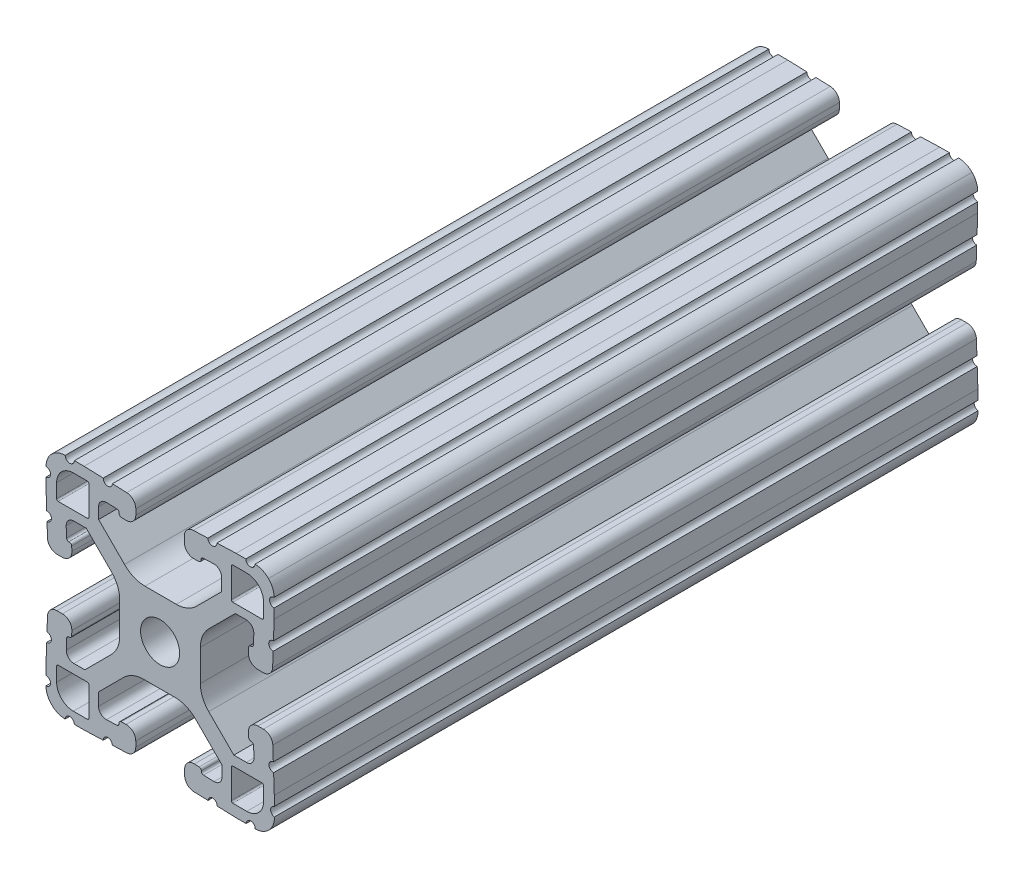
SolidWorks part; units mm, degrees
material "6061-T6 (SS)"
ref_plane "Front Plane" through (0, 0, 0) normal (0, 0, 1) x (1, 0, 0)
ref_plane "Top Plane" through (0, 0, 0) normal (0, 1, 0) x (1, 0, 0)
ref_plane "Right Plane" through (0, 0, 0) normal (1, 0, 0) x (0, 0, -1)
ref_plane "Plane1" through (0, 0, -25.4) normal (0, 0, -1) x (-1, 0, 0)
sketch "Sketch1" plane through (0, 0, -25.4) normal (0, 0, -1) x (-1, 0, 0)
  line L0 (-83.3577, 88.2941) -> (-83.3577, 93.1709)
  line L1 (-83.1037, 93.4249) -> (-80.767, 93.4249)
  line L2 (-77.9729, 90.6309) -> (-77.9729, 88.2941)
  line L3 (-78.2269, 88.0401) -> (-83.1037, 88.0401)
  line L4 (-83.3577, 59.2291) -> (-83.3577, 64.1059)
  line L5 (-83.1037, 64.3599) -> (-78.2269, 64.3599)
  line L6 (-77.9729, 64.1059) -> (-77.9729, 61.7691)
  line L7 (-80.767, 58.9751) -> (-83.1037, 58.9751)
  line L8 (-107.1423, 93.1709) -> (-107.1423, 88.2941)
  line L9 (-107.3963, 88.0401) -> (-112.2731, 88.0401)
  line L10 (-112.5271, 88.2941) -> (-112.5271, 90.6309)
  line L11 (-109.733, 93.4249) -> (-107.3963, 93.4249)
  line L12 (-107.1423, 64.1059) -> (-107.1423, 59.2291)
  line L13 (-107.3963, 58.9751) -> (-109.733, 58.9751)
  line L14 (-112.5271, 61.7691) -> (-112.5271, 64.1059)
  line L15 (-112.2731, 64.3599) -> (-107.3963, 64.3599)
  line L16 (-88.0437, 91.8626) -> (-86.2967, 91.9236)
  line L17 (-84.9824, 90.6544) -> (-84.9824, 88.8002)
  line L18 (-84.9824, 88.8002) -> (-89.3066, 84.476)
  line L19 (-92.7196, 83.0295) -> (-97.9616, 83.0295)
  line L20 (-101.3202, 84.4207) -> (-105.516, 88.6165)
  line L21 (-105.516, 88.6165) -> (-105.516, 90.7313)
  line L22 (-104.2017, 92.0006) -> (-102.4547, 91.9396)
  line L23 (-101.7262, 91.1059) -> (-100.9297, 91.0781)
  line L24 (-99.2999, 92.6519) -> (-99.2999, 93.5668)
  line L25 (-100.8197, 95.1407) -> (-103.2119, 95.2242)
  line L26 (-104.735, 95.2774) -> (-107.9359, 95.3892)
  line L27 (-107.9359, 95.3892) -> (-109.5615, 95.3892)
  line L28 (-114.2859, 90.6648) -> (-114.2859, 89.0392)
  line L29 (-114.2859, 89.0392) -> (-114.1741, 85.8383)
  line L30 (-114.1209, 84.3152) -> (-114.0374, 81.9231)
  line L31 (-112.4635, 80.4032) -> (-111.5486, 80.4032)
  line L32 (-109.9748, 82.033) -> (-110.0026, 82.8295)
  line L33 (-110.8377, 83.5577) -> (-110.8987, 85.3047)
  line L34 (-109.6294, 86.619) -> (-107.8072, 86.619)
  line L35 (-107.8072, 86.619) -> (-103.3649, 82.1768)
  line L36 (-101.9737, 78.8182) -> (-101.9737, 73.576)
  line L37 (-103.3649, 70.2174) -> (-107.5607, 66.0217)
  line L38 (-107.5607, 66.0217) -> (-109.6524, 66.0217)
  line L39 (-110.9217, 67.336) -> (-110.8607, 69.083)
  line L40 (-110.0322, 69.8124) -> (-110.0043, 70.6089)
  line L41 (-111.5782, 72.2387) -> (-112.4931, 72.2387)
  line L42 (-114.0669, 70.7189) -> (-114.1505, 68.3267)
  line L43 (-114.2036, 66.8036) -> (-114.3154, 63.6027)
  line L44 (-114.3154, 63.6027) -> (-114.3154, 61.9626)
  line L45 (-109.6111, 57.1437) -> (-107.9855, 57.1437)
  line L46 (-107.9855, 57.1437) -> (-104.7846, 57.2555)
  line L47 (-103.2615, 57.3086) -> (-100.8694, 57.3922)
  line L48 (-99.3495, 58.966) -> (-99.3495, 59.8809)
  line L49 (-100.9794, 61.4548) -> (-101.7758, 61.4269)
  line L50 (-102.5054, 60.599) -> (-104.2524, 60.538)
  line L51 (-105.5667, 61.8072) -> (-105.5667, 63.6295)
  line L52 (-105.5667, 63.6295) -> (-101.1311, 68.065)
  line L53 (-97.7725, 69.4562) -> (-92.5304, 69.4562)
  line L54 (-89.1717, 68.065) -> (-84.976, 63.8692)
  line L55 (-84.976, 63.8692) -> (-84.976, 61.7811)
  line L56 (-86.2903, 60.5118) -> (-88.0373, 60.5728)
  line L57 (-88.7596, 61.4332) -> (-89.5561, 61.461)
  line L58 (-91.1859, 59.8872) -> (-91.1859, 58.9723)
  line L59 (-89.6661, 57.3985) -> (-87.2739, 57.3149)
  line L60 (-85.7508, 57.2617) -> (-82.5499, 57.15)
  line L61 (-82.5499, 57.15) -> (-80.9244, 57.15)
  line L62 (-76.2, 61.8744) -> (-76.2, 63.4999)
  line L63 (-76.2, 63.4999) -> (-76.3117, 66.7008)
  line L64 (-76.3649, 68.2239) -> (-76.4484, 70.6161)
  line L65 (-78.0223, 72.1359) -> (-78.9372, 72.1359)
  line L66 (-80.511, 70.5061) -> (-80.4832, 69.7096)
  line L67 (-79.6552, 68.9801) -> (-79.5942, 67.2331)
  line L68 (-80.8634, 65.9188) -> (-82.6857, 65.9188)
  line L69 (-82.6857, 65.9188) -> (-87.1213, 70.3543)
  line L70 (-88.5125, 73.7128) -> (-88.5126, 78.955)
  line L71 (-87.1214, 82.3137) -> (-82.9257, 86.5095)
  line L72 (-82.9257, 86.5095) -> (-80.8375, 86.5095)
  line L73 (-79.5682, 85.1951) -> (-79.6293, 83.4482)
  line L74 (-80.4896, 82.7258) -> (-80.5175, 81.9294)
  line L75 (-78.9436, 80.2995) -> (-78.0287, 80.2995)
  line L76 (-76.4549, 81.8194) -> (-76.3713, 84.2115)
  line L77 (-76.3182, 85.7346) -> (-76.2064, 88.9355)
  line L78 (-76.2064, 88.9355) -> (-76.2064, 90.5611)
  line L79 (-80.9308, 95.2855) -> (-82.5564, 95.2855)
  line L80 (-82.5564, 95.2855) -> (-85.7573, 95.1737)
  line L81 (-87.2803, 95.1205) -> (-89.6725, 95.037)
  line L82 (-91.1924, 93.4632) -> (-91.1924, 92.5483)
  line L83 (-89.5625, 90.9744) -> (-88.7661, 91.0023)
  arc A0 (-83.3577, 93.1709) -> (-83.1037, 93.4249) centre (-83.1037, 93.1709) cw
  arc A1 (-80.767, 93.4249) -> (-77.9729, 90.6309) centre (-80.7669, 90.6309) cw
  arc A2 (-77.9729, 88.2941) -> (-78.2269, 88.0401) centre (-78.2269, 88.2941) cw
  arc A3 (-83.1037, 88.0401) -> (-83.3577, 88.2941) centre (-83.1037, 88.2941) cw
  arc A4 (-83.1037, 58.9751) -> (-83.3577, 59.2291) centre (-83.1037, 59.2291) cw
  arc A5 (-83.3577, 64.1059) -> (-83.1037, 64.3599) centre (-83.1037, 64.1059) cw
  arc A6 (-78.2269, 64.3599) -> (-77.9729, 64.1059) centre (-78.2269, 64.1059) cw
  arc A7 (-77.9729, 61.7691) -> (-80.767, 58.9751) centre (-80.7669, 61.7691) cw
  arc A8 (-107.3963, 93.4249) -> (-107.1423, 93.1709) centre (-107.3963, 93.1709) cw
  arc A9 (-107.1423, 88.2941) -> (-107.3963, 88.0401) centre (-107.3963, 88.2941) cw
  arc A10 (-112.2731, 88.0401) -> (-112.5271, 88.2941) centre (-112.2731, 88.2941) cw
  arc A11 (-112.5271, 90.6309) -> (-109.733, 93.4249) centre (-109.7331, 90.6309) cw
  arc A12 (-107.1423, 59.2291) -> (-107.3963, 58.9751) centre (-107.3963, 59.2291) cw
  arc A13 (-109.733, 58.9751) -> (-112.5271, 61.7691) centre (-109.7331, 61.7691) cw
  arc A14 (-112.5271, 64.1059) -> (-112.2731, 64.3599) centre (-112.2731, 64.1059) cw
  arc A15 (-107.3963, 64.3599) -> (-107.1423, 64.1059) centre (-107.3963, 64.1059) cw
  circle A16 centre (-95.25, 76.2) radius 3.2639
  arc A17 (-88.7661, 91.0023) -> (-88.3984, 91.383) centre (-88.7794, 91.383) ccw
  arc A18 (-88.3984, 91.383) -> (-88.0437, 91.8626) centre (-88.0304, 91.4819) cw
  arc A19 (-86.2967, 91.9236) -> (-84.9824, 90.6544) centre (-86.2524, 90.6544) cw
  arc A20 (-89.3066, 84.476) -> (-92.7196, 83.0295) centre (-92.7196, 87.7793) cw
  arc A21 (-97.9616, 83.0295) -> (-101.3202, 84.4207) centre (-97.9616, 87.7793) cw
  arc A22 (-105.516, 90.7313) -> (-104.2017, 92.0006) centre (-104.246, 90.7313) cw
  arc A23 (-102.4547, 91.9396) -> (-102.087, 91.5588) centre (-102.468, 91.5588) cw
  arc A24 (-102.087, 91.5588) -> (-101.7262, 91.1059) centre (-101.7129, 91.4867) ccw
  arc A25 (-100.9297, 91.0781) -> (-99.2999, 92.6519) centre (-100.8747, 92.6519) ccw
  arc A26 (-99.2999, 93.5668) -> (-100.8197, 95.1407) centre (-100.8747, 93.5668) ccw
  arc A27 (-103.2119, 95.2242) -> (-104.735, 95.2774) centre (-103.9735, 95.2508) cw
  arc A28 (-109.5615, 95.3892) -> (-111.0855, 95.3892) centre (-110.3235, 95.3892) cw
  arc A29 (-111.0855, 95.3892) -> (-113.3432, 94.4465) centre (-111.0855, 92.2142) ccw
  arc A30 (-113.3432, 94.4465) -> (-114.2859, 92.1888) centre (-111.1109, 92.1888) ccw
  arc A31 (-114.2859, 92.1888) -> (-114.2859, 90.6648) centre (-114.2859, 91.4268) cw
  arc A32 (-114.1741, 85.8383) -> (-114.1209, 84.3152) centre (-114.1475, 85.0768) cw
  arc A33 (-114.0374, 81.9231) -> (-112.4635, 80.4032) centre (-112.4635, 81.978) ccw
  arc A34 (-111.5486, 80.4032) -> (-109.9748, 82.033) centre (-111.5486, 81.978) ccw
  arc A35 (-110.0026, 82.8295) -> (-110.3834, 83.1972) centre (-110.3834, 82.8162) ccw
  arc A36 (-110.3834, 83.1972) -> (-110.8377, 83.5577) centre (-110.4569, 83.571) cw
  arc A37 (-110.8987, 85.3047) -> (-109.6294, 86.619) centre (-109.6294, 85.349) cw
  arc A38 (-103.3649, 82.1768) -> (-101.9737, 78.8182) centre (-106.7235, 78.8182) cw
  arc A39 (-101.9737, 73.576) -> (-103.3649, 70.2174) centre (-106.7235, 73.576) cw
  arc A40 (-109.6524, 66.0217) -> (-110.9217, 67.336) centre (-109.6524, 67.2917) cw
  arc A41 (-110.8607, 69.083) -> (-110.4799, 69.4507) centre (-110.4799, 69.0697) cw
  arc A42 (-110.4799, 69.4507) -> (-110.0322, 69.8124) centre (-110.413, 69.8257) ccw
  arc A43 (-110.0043, 70.6089) -> (-111.5782, 72.2387) centre (-111.5782, 70.6639) ccw
  arc A44 (-112.4931, 72.2387) -> (-114.0669, 70.7189) centre (-112.4931, 70.6639) ccw
  arc A45 (-114.1505, 68.3267) -> (-114.2036, 66.8036) centre (-114.1771, 67.5652) cw
  arc A46 (-114.3154, 61.9626) -> (-114.3332, 60.4644) centre (-114.4639, 61.2152) cw
  arc A47 (-114.3332, 60.4644) -> (-113.3928, 58.0864) centre (-111.1605, 60.3441) ccw
  arc A48 (-113.3928, 58.0864) -> (-111.1351, 57.1437) centre (-111.1351, 60.3187) ccw
  arc A49 (-111.1351, 57.1437) -> (-109.6111, 57.1437) centre (-110.3731, 57.1437) cw
  arc A50 (-104.7846, 57.2555) -> (-103.2615, 57.3086) centre (-104.0231, 57.2821) cw
  arc A51 (-100.8694, 57.3922) -> (-99.3495, 58.966) centre (-100.9243, 58.966) ccw
  arc A52 (-99.3495, 59.8809) -> (-100.9794, 61.4548) centre (-100.9243, 59.8809) ccw
  arc A53 (-101.7758, 61.4269) -> (-102.1435, 61.0462) centre (-101.7625, 61.0462) ccw
  arc A54 (-102.1435, 61.0462) -> (-102.5054, 60.599) centre (-102.5187, 60.9797) cw
  arc A55 (-104.2524, 60.538) -> (-105.5667, 61.8072) centre (-104.2967, 61.8072) cw
  arc A56 (-101.1311, 68.065) -> (-97.7725, 69.4562) centre (-97.7725, 64.7064) cw
  arc A57 (-92.5304, 69.4562) -> (-89.1717, 68.065) centre (-92.5304, 64.7064) cw
  arc A58 (-84.976, 61.7811) -> (-86.2903, 60.5118) centre (-86.246, 61.7811) cw
  arc A59 (-88.0373, 60.5728) -> (-88.405, 60.9536) centre (-88.024, 60.9536) cw
  arc A60 (-88.405, 60.9536) -> (-88.7596, 61.4332) centre (-88.7729, 61.0524) ccw
  arc A61 (-89.5561, 61.461) -> (-91.1859, 59.8872) centre (-89.6111, 59.8872) ccw
  arc A62 (-91.1859, 58.9723) -> (-89.6661, 57.3985) centre (-89.6111, 58.9723) ccw
  arc A63 (-87.2739, 57.3149) -> (-85.7508, 57.2617) centre (-86.5124, 57.2883) cw
  arc A64 (-80.9244, 57.15) -> (-79.4004, 57.15) centre (-80.1624, 57.15) cw
  arc A65 (-79.4004, 57.15) -> (-77.1426, 58.0927) centre (-79.4004, 60.325) ccw
  arc A66 (-77.1426, 58.0927) -> (-76.2, 60.3504) centre (-79.375, 60.3504) ccw
  arc A67 (-76.2, 60.3504) -> (-76.2, 61.8744) centre (-76.2, 61.1124) cw
  arc A68 (-76.3117, 66.7008) -> (-76.3649, 68.2239) centre (-76.3383, 67.4624) cw
  arc A69 (-76.4484, 70.6161) -> (-78.0223, 72.1359) centre (-78.0223, 70.5611) ccw
  arc A70 (-78.9372, 72.1359) -> (-80.511, 70.5061) centre (-78.9372, 70.5611) ccw
  arc A71 (-80.4832, 69.7096) -> (-80.1024, 69.342) centre (-80.1024, 69.723) ccw
  arc A72 (-80.1024, 69.342) -> (-79.6552, 68.9801) centre (-80.036, 68.9668) cw
  arc A73 (-79.5942, 67.2331) -> (-80.8634, 65.9188) centre (-80.8634, 67.1888) cw
  arc A74 (-87.1213, 70.3543) -> (-88.5125, 73.7128) centre (-83.7627, 73.7129) cw
  arc A75 (-88.5126, 78.955) -> (-87.1214, 82.3137) centre (-83.7628, 78.9551) cw
  arc A76 (-80.8375, 86.5095) -> (-79.5682, 85.1951) centre (-80.8375, 85.2395) cw
  arc A77 (-79.6293, 83.4482) -> (-80.01, 83.0805) centre (-80.01, 83.4615) cw
  arc A78 (-80.01, 83.0805) -> (-80.4896, 82.7258) centre (-80.1089, 82.7125) ccw
  arc A79 (-80.5175, 81.9294) -> (-78.9436, 80.2995) centre (-78.9436, 81.8743) ccw
  arc A80 (-78.0287, 80.2995) -> (-76.4549, 81.8194) centre (-78.0287, 81.8743) ccw
  arc A81 (-76.3713, 84.2115) -> (-76.3182, 85.7346) centre (-76.3448, 84.9731) cw
  arc A82 (-76.2064, 90.5611) -> (-76.2064, 92.0851) centre (-76.2064, 91.3231) cw
  arc A83 (-76.2064, 92.0851) -> (-77.1491, 94.3428) centre (-79.3814, 92.0851) ccw
  arc A84 (-77.1491, 94.3428) -> (-79.4068, 95.2855) centre (-79.4068, 92.1105) ccw
  arc A85 (-79.4068, 95.2855) -> (-80.9308, 95.2855) centre (-80.1688, 95.2855) cw
  arc A86 (-85.7573, 95.1737) -> (-87.2803, 95.1205) centre (-86.5188, 95.1471) cw
  arc A87 (-89.6725, 95.037) -> (-91.1924, 93.4632) centre (-89.6176, 93.4632) ccw
  arc A88 (-91.1924, 92.5483) -> (-89.5625, 90.9744) centre (-89.6176, 92.5483) ccw
extrude "Boss-Extrude1" add sketch "Sketch1" against normal blind 117.475
